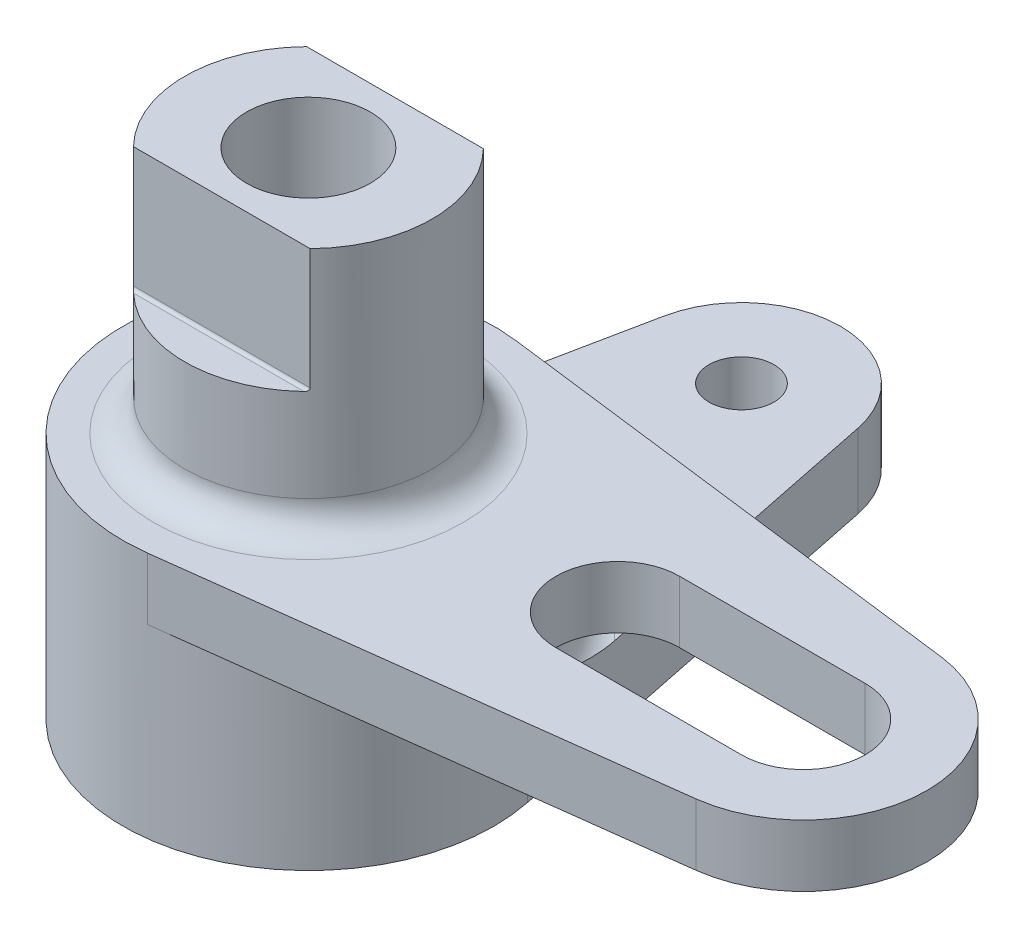
SolidWorks part; units mm, degrees
ref_plane "Piano frontale" through (0, 0, 0) normal (0, 0, 1) x (1, 0, 0)
ref_plane "Piano superiore" through (0, 0, 0) normal (0, 1, 0) x (1, 0, 0)
ref_plane "Piano destro" through (0, 0, 0) normal (1, 0, 0) x (0, 0, -1)
sketch "Schizzo1" plane through (0, 0, 0) normal (0, 1, 0) x (1, 0, 0)
  line L0 (0, 101.7293) -> (0, -73.8454) construction
  line L1 (-15.6767, 73.2) -> (-29.3939, 6)
  line L2 (15.6767, 73.2) -> (29.3939, 6)
  line L3 (-79.4489, 0) -> (107.7803, 0) construction
  line L4 (-14.2829, 14) -> (14.2829, 14)
  line L5 (-14.2829, -14) -> (14.2829, -14)
  circle A0 centre (0, 0) radius 30
  circle A1 centre (0, 0) radius 20
  circle A2 centre (0, 0) radius 10
  arc A3 (15.6767, 73.2) -> (-15.6767, 73.2) centre (0, 70) ccw
  point P18 (0, 0)
  point P19 (0, 0)
  dimension "D2" = 60
  dimension "D3" = 40
  dimension "D4" = 20
  dimension "D5" = 32
  dimension "D1" = 70
  dimension "D6" = 28
extrude "Estrusione-Estrusione1" add sketch "Schizzo1" along normal blind 40 contours A0 L0 A1 | L0 A0 A1 region at (18.5494, 0, -22.7183) region at (-0.6708, 0, -25)
extrude "Estrusione-Estrusione2" add sketch "Schizzo1<4>" along normal blind 80 contours L5 A1 L4 A2 region at (0, 0, -13.5117)
sketch "Schizzo1<4>" plane through (0, 0, 0) normal (0, 1, 0) x (1, 0, 0) same geometry as "Schizzo1"
extrude "Estrusione-Estrusione3" add sketch "Schizzo1<5>" along normal blind 60 contours L4 A1 | L5 A1 region at (0, 0, -16.4338) region at (0, 0, 16.4338)
sketch "Schizzo1<5>" plane through (0, 0, 0) normal (0, 1, 0) x (1, 0, 0) same geometry as "Schizzo1"
extrude "Estrusione-Estrusione4" add sketch "Schizzo1<6>" along normal blind 12 contours L2 A3 L1 A0 region at (0, 0, -51.1568)
sketch "Schizzo1<6>" plane through (0, 0, 0) normal (0, 1, 0) x (1, 0, 0) same geometry as "Schizzo1"
sketch "Schizzo2" plane through (0, 40, 0) normal (0, 1, 0) x (1, 0, 0)
  line L0 (-62.1694, 0) -> (98.999, 0) construction
  line L1 (3.75, 29.7647) -> (82.5, 19.8431)
  line L2 (3.75, -29.7647) -> (82.5, -19.8431)
  line L3 (50, 0) -> (80, 0) construction
  line L4 (50, 10) -> (80, 10)
  line L5 (50, -10) -> (80, -10)
  arc A0 (82.5, -19.8431) -> (82.5, 19.8431) centre (80, 0) ccw
  circle A1 centre (0, 0) radius 30 construction
  arc A4 (50, 10) -> (50, -10) centre (50, 0) ccw
  arc A5 (80, -10) -> (80, 10) centre (80, 0) ccw
  point P9 (65, 0)
  point P17 (0, 0)
  circle M9 centre (0, 0) radius 30
  dimension "D1" = 40
  dimension "D4" = 10
  dimension "D2" = 80
  dimension "D3" = 30
extrude "Estrusione-Estrusione5" add sketch "Schizzo2" against normal blind 10 contours L2 A0 L1 A5 L5 A4 L4 M9 region at (42.9835, 40, -23.6811)
hole_wizard "Foro filettato M12x1.5-1" positions "Schizzo3" profile "Schizzo4" tap size "M12x1.5" standard "ISO" end condition through all
sketch "Schizzo3" plane through (0, 12, 0) normal (0, 1, 0) x (1, 0, 0)
  line L0 (0, 0) -> (0, 92.4653) construction
  line L2 (-45.0761, 70) -> (38.8825, 70) construction
  point P9 (0, 70)
  point P12 (0, 0)
  dimension "D1" = 70
sketch "Schizzo4" plane through (0, 12, -70) normal (1, 0, 0) x (0, 0, 1)
  line L0 (0, 0) -> (0, 12)
  line L1 (0, 12) -> (5.25, 12)
  line L2 (5.25, 12) -> (5.25, 0)
  line L5 (5.25, 0) -> (0, 0)
  line L11 (0, -6.35) -> (0, 107.95) construction
  dimension "Thru Tap Drill Dia." = 10.5
  dimension "Thru Tap Drill Depth" = 12
cosmetic thread "Filettatura del foro1" parameters "D2"=12
fillet "Raccordo1" radius 5 2 edges at (0, 40, 20) (0, 12, -30)
fillet "Raccordo2" radius 0.5 2 edges at (0, 60, -14) (0, 60, 14)
sketch "Schizzo5" plane through (0, 0, 0) normal (0, -1, 0) x (1, 0, 0)
  line L0 (0, 0) -> (0, -103.5956)
